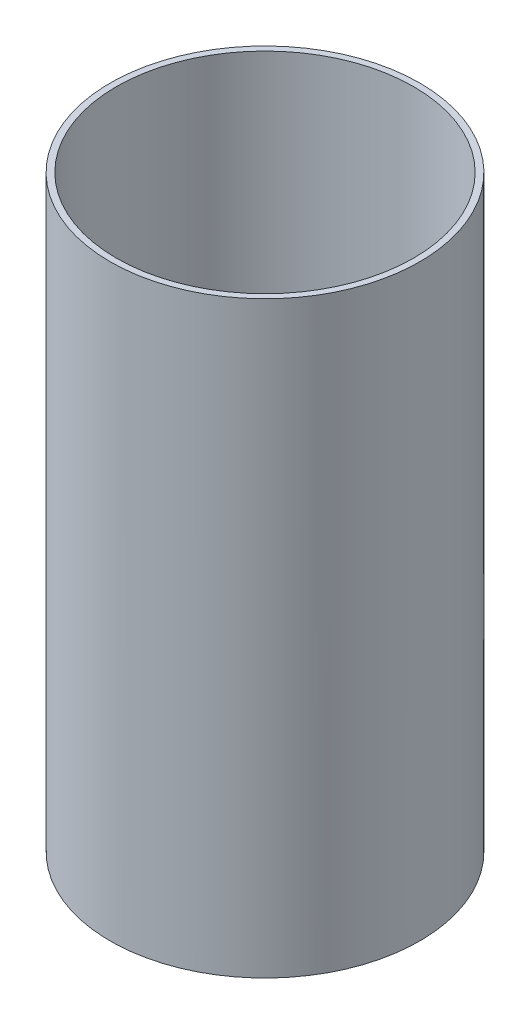
SolidWorks part; units mm, degrees
ref_plane "Спереди" through (0, 0, 0) normal (0, 0, 1) x (1, 0, 0)
ref_plane "Сверху" through (0, 0, 0) normal (0, 1, 0) x (1, 0, 0)
ref_plane "Справа" through (0, 0, 0) normal (1, 0, 0) x (0, 0, -1)
sketch "Sketch1" plane through (0, 0, 0) normal (0, 1, 0) x (1, 0, 0)
  circle A0 centre (0, 0) radius 25
  circle A1 centre (0, 0) radius 24
  dimension "D1" = 50
  dimension "D2" = 48
extrude "Boss-Extrude1" add sketch "Sketch1" along normal blind 85
sketch "Sketch2" plane through (0, 0, 0) normal (0, -1, 0) x (1, 0, 0)
  circle A0 centre (0, 0) radius 25
  circle A1 centre (0, 0) radius 24
extrude "Boss-Extrude2" add sketch "Sketch2" along normal blind 10
